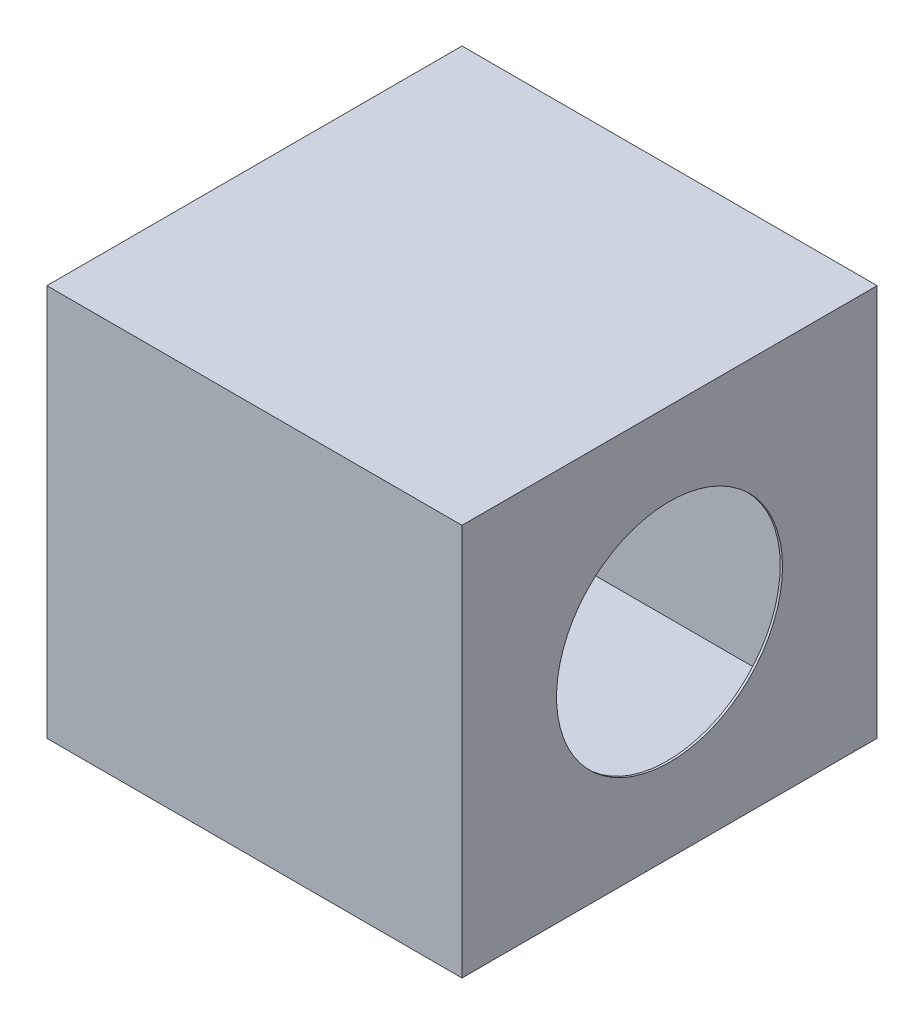
SolidWorks part; units mm, degrees
ref_plane "Alzado" through (0, 0, 0) normal (0, 0, 1) x (1, 0, 0)
ref_plane "Planta" through (0, 0, 0) normal (0, 1, 0) x (1, 0, 0)
ref_plane "Vista lateral" through (0, 0, 0) normal (1, 0, 0) x (0, 0, -1)
sketch "Croquis1" plane through (0, 0, 0) normal (0, 0, 1) x (1, 0, 0)
  line L1 (-90, 85) -> (90, 85)
  line L2 (-90, 85) -> (-90, -85)
  line L3 (-90, -85) -> (90, -85)
  line L4 (90, 85) -> (90, -85)
  line L5 (0, -85) -> (0, 85) construction
  line L6 (-90, 0) -> (90, 0) construction
  point P0 (0, 0)
  dimension "D1" = 180
  dimension "D2" = 170
extrude "Saliente-Extruir1" add sketch "Croquis1" along normal mid plane 180
sketch "Croquis2" plane through (-90, 0, 0) normal (-1, 0, 0) x (0, 0, 1)
  circle A0 centre (0, 0) radius 49
  dimension "D1" = 98
extrude "Cortar-Extruir1" cut sketch "Croquis2" against normal blind 1
sketch "Croquis3" plane through (90, 0, 0) normal (1, 0, 0) x (0, 0, -1)
  circle A0 centre (0, 0) radius 49
  dimension "D1" = 98
extrude "Cortar-Extruir2" cut sketch "Croquis3" against normal blind 1
shell "Vaciado1" thickness 1 removed face at (-89, 0, 49) removed face at (89, 0, -49)
